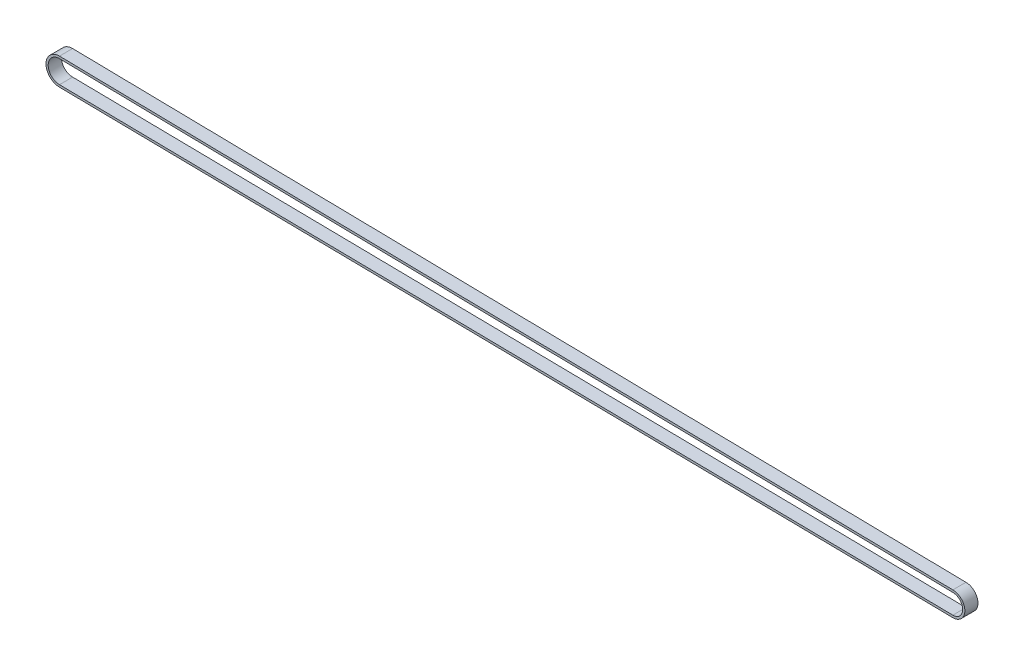
SolidWorks part; units mm, degrees
ref_plane "Front Plane" through (0, 0, 0) normal (0, 0, 1) x (1, 0, 0)
ref_plane "Top Plane" through (0, 0, 0) normal (0, 1, 0) x (1, 0, 0)
ref_plane "Right Plane" through (0, 0, 0) normal (1, 0, 0) x (0, 0, -1)
sketch "Sketch1" plane through (0, 0, 0) normal (0, 0, 1) x (1, 0, 0)
  line L0 (0, 5.15) -> (407.9379, -1.9706)
  line L1 (0, 5.15) -> (0, -5.15) construction
  line L2 (407.9379, -1.9706) -> (407.9379, -10.9706) construction
  line L3 (407.9379, -10.9706) -> (0, -5.15)
  line L4 (407.9379, -0.9706) -> (0, 6.15)
  line L5 (0, -6.15) -> (407.9379, -11.9706)
  arc A0 (0.1797, 5.1469) -> (0, -5.15) centre (0, 0) ccw
  arc A1 (407.9379, -10.9706) -> (407.9379, -1.9706) centre (407.9379, -6.4706) ccw
  arc A2 (0.2146, 6.1463) -> (0, -6.15) centre (0, 0) ccw
  arc A3 (407.7809, -11.9683) -> (407.9379, -0.9706) centre (407.9379, -6.4706) ccw
  dimension "D1" = 10.3
  dimension "D5" = 12.3
  dimension "D6" = 11
  dimension "D2" = 408
  dimension "D3" = 89
  dimension "D4" = 9
extrude "Boss-Extrude1" add sketch "Sketch1" along normal blind 6 contours L5 A3 L4 A2 A1 L3 A0 L0 region at (413.0179, -6.4706, 0)
